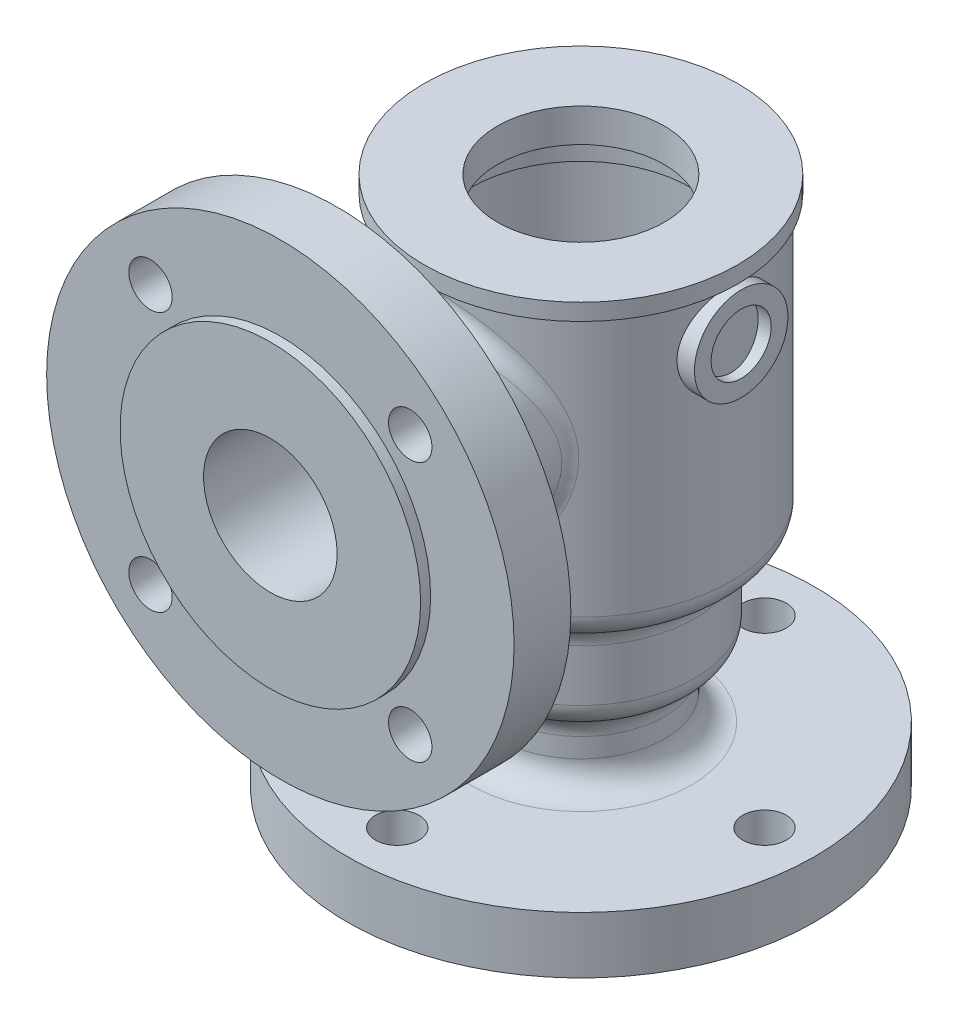
SolidWorks part; units mm, degrees
ref_plane "Front Plane" through (0, 0, 0) normal (0, 0, 1) x (1, 0, 0)
ref_plane "Top Plane" through (0, 0, 0) normal (0, 1, 0) x (1, 0, 0)
ref_plane "Right Plane" through (0, 0, 0) normal (1, 0, 0) x (0, 0, -1)
sketch "Sketch2" plane through (0, 0, 0) normal (0, 0, 1) x (1, 0, 0)
  line L0 (-109.6215, 94.6711) -> (-87.6215, 94.6711)
  line L27 (-62.6215, 103.6263) -> (-62.6215, -68.7043) construction
  line L28 (-87.6215, 94.6711) -> (-87.6215, 84.6711)
  line L29 (-87.6215, 84.6711) -> (-95.6215, 84.6711)
  line L30 (-95.6215, 84.6711) -> (-95.6215, 74.6711)
  line L31 (-95.6215, 74.6711) -> (-100.6215, 74.6711)
  line L32 (-100.6215, 74.6711) -> (-100.6215, 7.6711)
  line L33 (-109.6215, 94.6711) -> (-109.6215, 89.6711)
  line L34 (-109.6215, 89.6711) -> (-107.6215, 89.6711)
  line L35 (-107.6215, 89.6711) -> (-107.6215, 11.5611)
  line L36 (-100.6215, 7.6711) -> (-95.6215, 7.6711)
  line L37 (-95.6215, 7.6711) -> (-95.6215, 12.6711)
  line L38 (-95.6215, 12.6711) -> (-90.6215, 12.6711)
  line L39 (-90.6215, 12.6711) -> (-90.6215, -17.3289)
  line L40 (-90.6215, -17.3289) -> (-82.6215, -17.3289)
  line L41 (-82.6215, -17.3289) -> (-82.6215, -67.3289)
  line L42 (-82.6215, -67.3289) -> (-107.6215, -67.3289)
  line L43 (-107.6215, -67.3289) -> (-107.6215, -64.3289)
  line L44 (-107.6215, -64.3289) -> (-132.6215, -64.3289)
  line L45 (-132.6215, -64.3289) -> (-132.6215, -47.3289)
  line L46 (-96.6215, -3.6376) -> (-96.6215, -19.1376)
  line L47 (-87.6215, -33.5251) -> (-87.6215, -39.3351)
  line L48 (-132.6215, -47.3289) -> (-95.6215, -47.3351)
  arc A0 (-107.6215, 11.5611) -> (-102.1215, 3.9617) centre (-99.6215, 11.5611) ccw
  arc A1 (-102.1215, 3.9617) -> (-96.6215, -3.6376) centre (-104.6215, -3.6376) cw
  arc A2 (-96.6215, -19.1376) -> (-92.1215, -26.3314) centre (-88.6215, -19.1376) ccw
  arc A3 (-92.1215, -26.3314) -> (-87.6215, -33.5251) centre (-95.6215, -33.5251) cw
  arc A4 (-87.6215, -39.3351) -> (-95.6215, -47.3351) centre (-95.6215, -39.3351) cw
  dimension "D23" = 8
  dimension "D24" = 8
  dimension "D25" = 8
  dimension "D26" = 8
  dimension "D27" = 8
  dimension "D1" = 22
  dimension "D2" = 5
  dimension "D3" = 2
  dimension "D4" = 20
  dimension "D5" = 10
  dimension "D6" = 8
  dimension "D7" = 10
  dimension "D8" = 5
  dimension "D9" = 67
  dimension "D10" = 5
  dimension "D11" = 5
  dimension "D12" = 5
  dimension "D13" = 30
  dimension "D14" = 8
  dimension "D15" = 50
  dimension "D16" = 25
  dimension "D17" = 3
  dimension "D18" = 25
  dimension "D19" = 17
  dimension "D20" = 78.11
  dimension "D21" = 15.5
  dimension "D22" = 5.81
  dimension "D28" = 5
  dimension "D29" = 6
revolve "Revolve2" add sketch "Sketch2" angle 360 about L27
ref_plane "Plane1" through (0, 0, 73) normal (0, 0, 1) x (1, 0, 0)
sketch "Sketch4" plane through (0, 0, 73) normal (0, 0, 1) x (1, 0, 0)
  line L0 (-132.6215, -64.3289) -> (7.3785, -64.3289) construction
  circle A0 centre (-62.6215, 52.6711) radius 30
  circle A1 centre (-62.6215, 52.6711) radius 20
  circle A2 centre (-62.6215, 52.6711) radius 45
  circle A3 centre (-62.6215, 52.6711) radius 70
  point P5 (0, 0)
  dimension "D1" = 117
extrude "Cut-Extrude1" cut sketch "Sketch4" against normal up to next contours A1 region at (-62.6215, 52.6711, 73)
sketch "Sketch6" plane through (0, 0, 73) normal (0, 0, 1) x (1, 0, 0)
  circle A0 centre (-62.6215, 52.6711) radius 20
  circle A1 centre (-62.6215, 52.6711) radius 30
extrude "Boss-Extrude1" add sketch "Sketch6" against normal up to surface (32.6887 mm away) up to face at (-82.4522, 55.2674, 40.3948)
sketch "Sketch7" plane through (0, 0, 73) normal (0, 0, 1) x (1, 0, 0)
  circle A1 centre (-62.6215, 52.6711) radius 70
  circle A2 centre (-62.6215, 52.6711) radius 20
extrude "Boss-Extrude4" add sketch "Sketch7" along normal blind 17
sketch "Sketch8" plane through (0, 0, 90) normal (0, 0, 1) x (1, 0, 0)
  circle A0 centre (-62.6215, 52.6711) radius 20
  circle A1 centre (-62.6215, 52.6711) radius 45
extrude "Boss-Extrude5" add sketch "Sketch8" along normal blind 3
sketch "Sketch9" plane through (0, 0, 90) normal (0, 0, 1) x (1, 0, 0)
  line L0 (-62.6215, 52.6711) -> (-62.6215, 109.0963) construction
  line L1 (-101.5124, 91.5619) -> (-62.6215, 52.6711) construction
  circle A4 centre (-101.5124, 91.5619) radius 6.5
  circle A5 centre (-23.7306, 91.5619) radius 6.5
  circle A6 centre (-23.7306, 13.7802) radius 6.5
  circle A7 centre (-101.5124, 13.7802) radius 6.5
  point P14 (-62.6215, 52.6711)
  dimension "D1" = 55
  dimension "D2" = 13
  dimension "D3" = 45
  dimension "D4" = 4
extrude "Cut-Extrude2" cut sketch "Sketch9" against normal up to next
sketch "Sketch10" plane through (0, -64.3289, 0) normal (0, -1, 0) x (1, 0, 0)
  line L0 (-7.6215, 0) -> (-62.6215, 0) construction
  circle A0 centre (-7.6215, 0) radius 6.5
  circle A1 centre (-62.6215, -55) radius 6.5
  circle A2 centre (-117.6215, 0) radius 6.5
  circle A3 centre (-62.6215, 55) radius 6.5
  point P13 (-62.6215, 0)
  dimension "D1" = 55
  dimension "D2" = 4
extrude "Cut-Extrude3" cut sketch "Sketch10" against normal up to next
sketch "Sketch12" plane through (0, 0, 0) normal (0, 0, 1) x (1, 0, 0)
  line L0 (-62.6215, 94.6711) -> (-62.6215, 11.5611) construction
  line L1 (-15.6215, 94.6711) -> (-109.6215, 94.6711) construction
  line L2 (-107.6215, 11.5611) -> (-17.6215, 11.5611) construction
  line L3 (-62.6215, 11.5611) -> (-14.6215, 11.5611) construction
  line L4 (-14.6215, 11.5611) -> (-14.6215, 74.5759) construction
  point P8 (0, 0)
  dimension "D1" = 48
ref_plane "Plane4" through (-14.6215, 0, 0) normal (1, 0, 0) x (0, 0, -1)
sketch "Sketch13" plane through (-14.6215, 0, 0) normal (1, 0, 0) x (0, 0, -1)
  line L0 (0, 94.6711) -> (0, 11.5611) construction
  line L1 (47, 94.6711) -> (-47, 94.6711) construction
  circle A0 centre (0, 74.6711) radius 9
  circle A1 centre (0, 74.6711) radius 14
  dimension "D1" = 18
  dimension "D2" = 28
  dimension "D3" = 20
extrude "Boss-Extrude7" add sketch "Sketch13" against normal up to surface (3 mm away) up to face at (-91.9685, 46.4462, 34.1138)
sketch "Sketch15" plane through (0, 94.6711, 0) normal (0, 1, 0) x (1, 0, 0)
  line L0 (-62.6215, 0) -> (-62.6215, 56.2516) construction
ref_plane "Plane5" through (-62.6215, 0, 0) normal (-1, 0, 0) x (0, 0, 1)
mirror "Mirror1" about plane through (-62.6215, 0, 0) normal (-1, 0, 0) of "Boss-Extrude7"
fillet "Fillet4" radius 5 1 edges at (-91.9685, 46.4462, 34.1138)
fillet "Fillet5" radius 5 1 edges at (-32.6215, 52.6711, 73)
